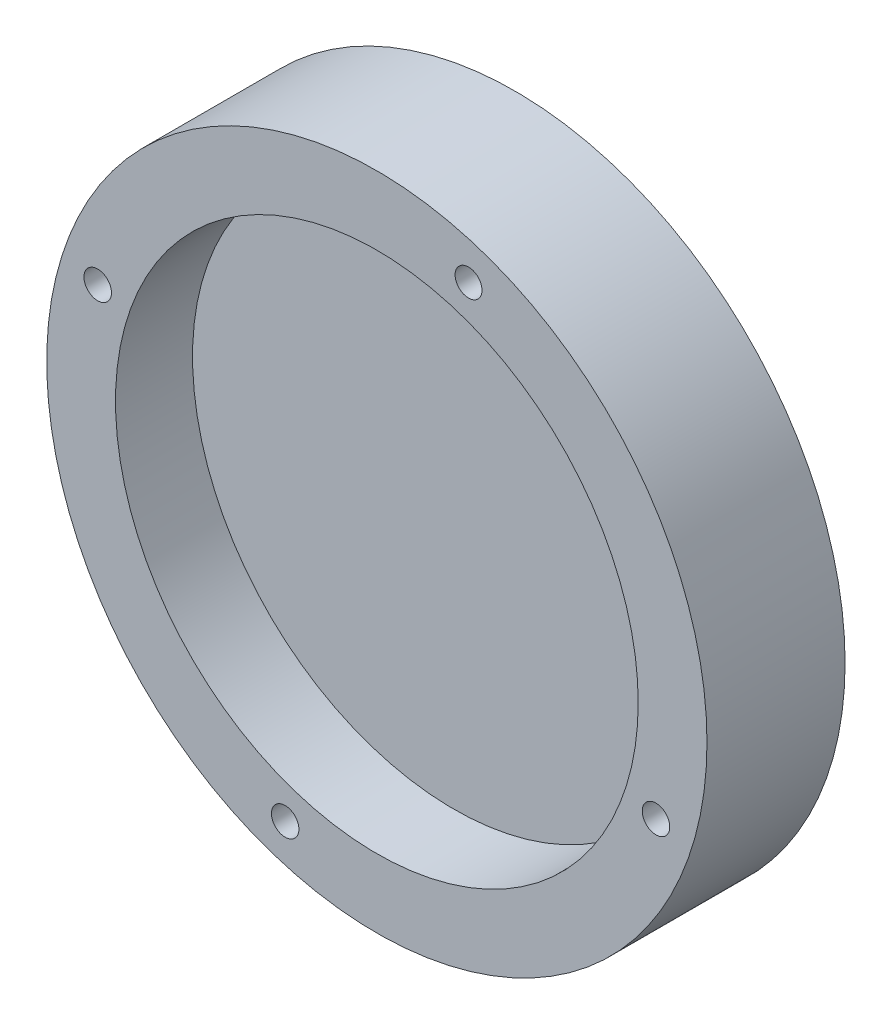
SolidWorks part; units mm, degrees
ref_plane "Front Plane" through (0, 0, 0) normal (0, 0, 1) x (1, 0, 0)
ref_plane "Top Plane" through (0, 0, 0) normal (0, 1, 0) x (1, 0, 0)
ref_plane "Right Plane" through (0, 0, 0) normal (1, 0, 0) x (0, 0, -1)
sketch "Sketch1" plane through (0, 0, 0) normal (0, 0, 1) x (1, 0, 0)
  circle A0 centre (0, 0) radius 60
  dimension "D1" = 120
extrude "Boss-Extrude1" add sketch "Sketch1" along normal blind 25.1
sketch "Sketch2" plane through (0, 0, 25.1) normal (0, 0, 1) x (1, 0, 0)
  circle A0 centre (-16.6647, -50.7331) radius 2.495
  circle A1 centre (-50.7331, 16.6647) radius 2.5
  circle A2 centre (16.6647, 50.7331) radius 2.4444
  circle A3 centre (50.7331, -16.6647) radius 2.5
sketch "Sketch3" plane through (0, 0, 25.1) normal (0, 0, 1) x (1, 0, 0)
  circle A0 centre (0, 0) radius 47.5
  dimension "D1" = 95
extrude "Cut-Extrude2" cut sketch "Sketch3" against normal blind 14
extrude "Cut-Extrude5" cut sketch "Sketch2" against normal through all both and the other way through all
sketch "Sketch6" plane through (0, 0, 0) normal (0, 0, -1) x (-1, 0, 0)
  circle A0 centre (11.9735, 47.2126) radius 3
  circle A1 centre (27.3813, 40.0293) radius 3
  circle A2 centre (-19.7177, -20.7629) radius 3
  circle A3 centre (-4.3099, -27.9462) radius 3
  dimension "D1" = 6
  dimension "D2" = 6
  dimension "D3" = 6
  dimension "D4" = 6
extrude "Cut-Extrude6" cut sketch "Sketch6" against normal blind 6
